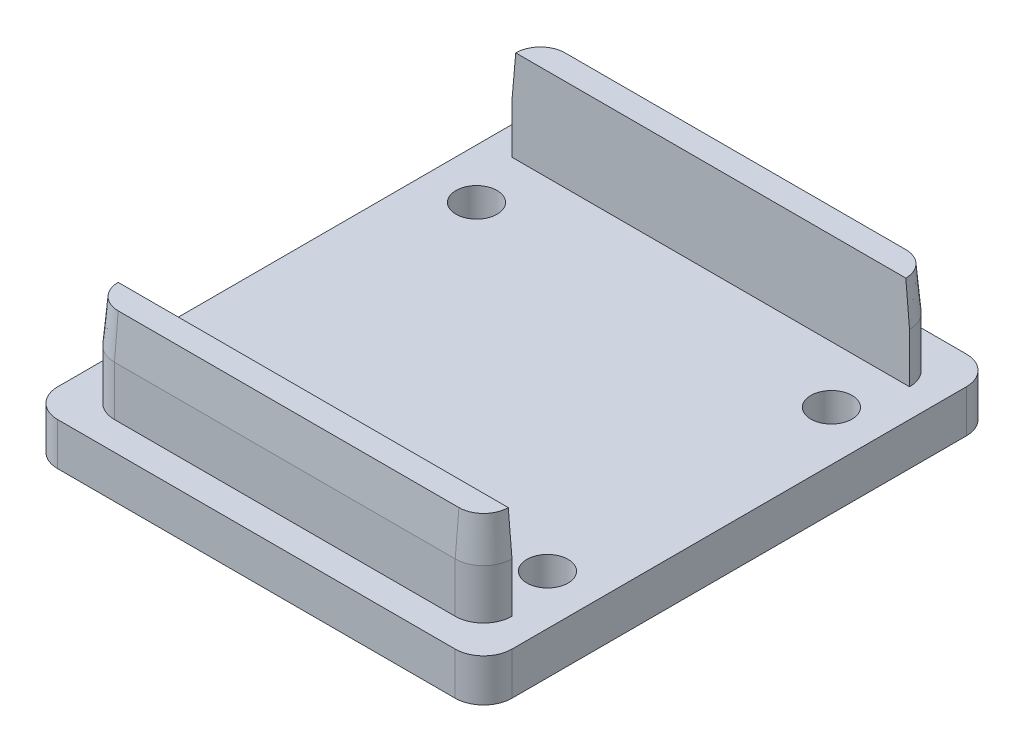
SolidWorks part; units mm, degrees
ref_plane "Front Plane" through (0, 0, 0) normal (0, 0, 1) x (1, 0, 0)
ref_plane "Top Plane" through (0, 0, 0) normal (0, 1, 0) x (1, 0, 0)
ref_plane "Right Plane" through (0, 0, 0) normal (1, 0, 0) x (0, 0, -1)
sketch "Sketch1" plane through (0, 0, 0) normal (0, 1, 0) x (1, 0, 0)
  line L1 (-16, -18) -> (16, -18)
  line L2 (-16, -18) -> (-16, 18)
  line L3 (-16, 18) -> (16, 18)
  line L4 (16, -18) -> (16, 18)
  line L5 (-16, -18) -> (16, 18) construction
  line L6 (-16, 18) -> (16, -18) construction
  point P0 (0, 0)
  dimension "D1" = 32
  dimension "D2" = 36
extrude "Boss-Extrude1" add sketch "Sketch1" along normal blind 3
sketch "Sketch4" plane through (0, 3, 0) normal (0, 1, 0) x (1, 0, 0)
  line L0 (-14, 16) -> (-14, 14)
  line L2 (-14, 14) -> (14, 14)
  line L3 (-16, 18) -> (-16, -18) construction
  line L4 (-14, -16) -> (-14, -14)
  line L5 (-14, -14) -> (14, -14)
  line L11 (-14, -16) -> (14, -16)
  line L13 (14, 16) -> (-14, 16)
  line L15 (16, 18) -> (-16, 18) construction
  line L17 (-16, -18) -> (16, -18) construction
  line L18 (14, 16) -> (14, -16) construction
  line L19 (14, 16) -> (14, 14)
  line L23 (14, -14) -> (14, -16)
  line L24 (16, -18) -> (16, 18) construction
  dimension "D1" = 2
  dimension "D2" = 2
  dimension "D3" = 2
  dimension "D4" = 2
  dimension "D5" = 2
  dimension "D6" = 2
  dimension "D7" = 2
extrude "Boss-Extrude3" add sketch "Sketch4" along normal blind 6.5
fillet "Fillet4" radius 2 8 edges at (14, 6.25, -16) (14, 6.25, 16) (-16, 1.5, 18) (16, 1.5, 18) (-16, 1.5, -18) (16, 1.5, -18) (-14, 6.25, 16) (-14, 6.25, -16)
chamfer "Chamfer2" distance 3 angle 5 6 edges at (13.4142, 9.5, 15.4142) (0, 9.5, 16) (13.4142, 9.5, -15.4142) (0, 9.5, -16) (-13.4142, 9.5, -15.4142) (-13.4142, 9.5, 15.4142) first distance on face at (13.2071, 6.25, 15.2071) first distance on face at (0, 6.25, 16) first distance on face at (13.2071, 6.25, -15.2071) first distance on face at (0, 6.25, -16) first distance on face at (-13.2071, 6.25, -15.2071) first distance on face at (-13.2071, 6.25, 15.2071)
sketch "Sketch5" plane through (0, 3, 0) normal (0, 1, 0) x (1, 0, 0)
  line L0 (-16, 0) -> (16, 0) construction
  line L1 (-16, 16) -> (-16, -16) construction
  line L2 (16, -16) -> (16, 16) construction
  line L3 (-13.7375, 14) -> (13.7375, 14) construction
  circle A0 centre (-12.5, 10) radius 1.45
  dimension "D1" = 2.9
  dimension "D2" = 4
  dimension "D3" = 3.5
extrude "Cut-Extrude1" cut sketch "Sketch5" against normal blind 2.3
mirror "Mirror1" about plane through (0, 0, 0) normal (1, 0, 0) of "Cut-Extrude1" second plane through (0, 0, 0) second plane normal (0, 0, 1)
